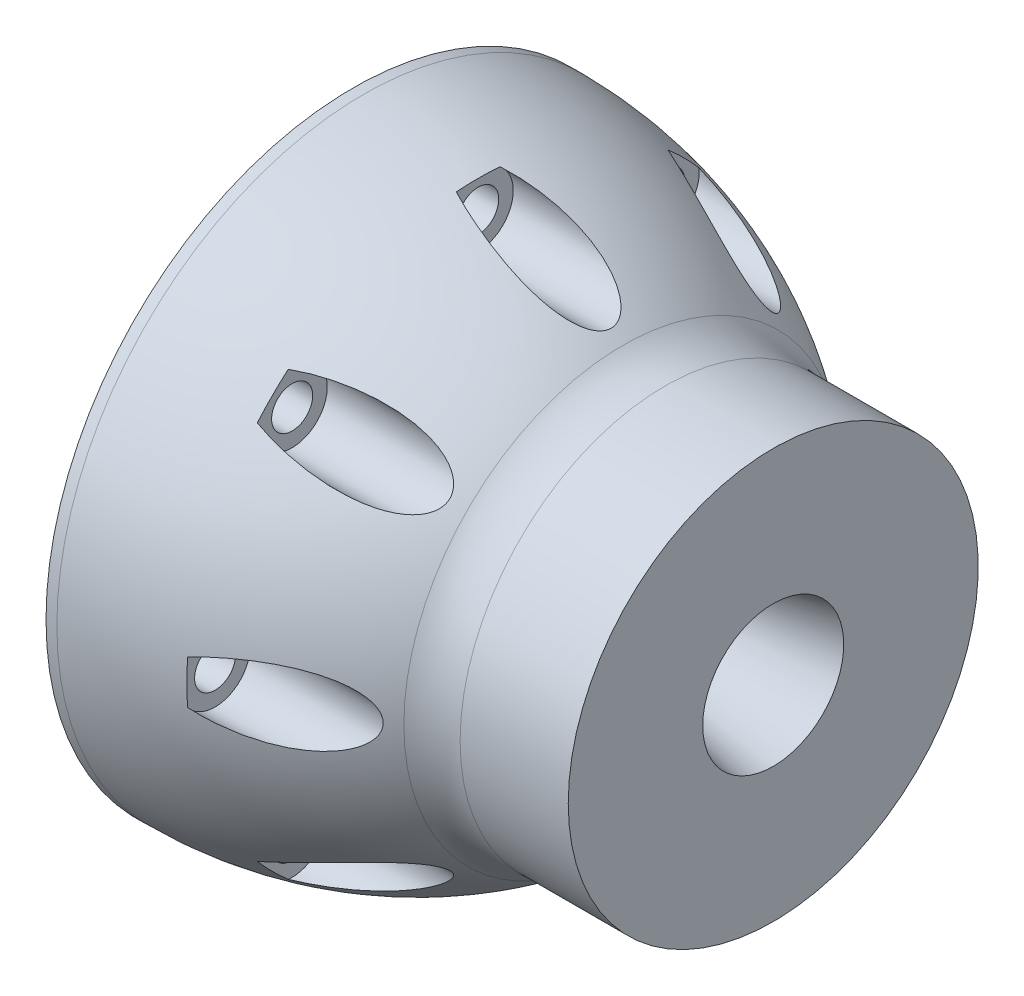
SolidWorks part; units mm, degrees
material "PLA (Polylactic Acid)"
ref_plane "Front Plane" through (0, 0, 0) normal (0, 0, 1) x (1, 0, 0)
ref_plane "Top Plane" through (0, 0, 0) normal (0, 1, 0) x (1, 0, 0)
ref_plane "Right Plane" through (0, 0, 0) normal (1, 0, 0) x (0, 0, -1)
sketch "Model" plane through (0, 0, 0) normal (0, 0, 1) x (1, 0, 0)
  line L0 (0, 19.051) -> (31.9536, 19.051)
  line L1 (38.3809, 16.3887) -> (49.0299, 5.7397)
  line L2 (0, 0) -> (61.8717, 0) construction
  arc A0 (38.3809, 16.3887) -> (31.9536, 19.051) centre (31.9536, 9.9615) ccw
  arc A1 (49.0299, 5.7397) -> (50.8, 5.0065) centre (50.8, 7.5097) ccw
  arc A2 (50.8, 5.0065) -> (51.2904, 5.055) centre (50.8, 7.5097) ccw
  spline S0 degree 2 poles (51.2904, 5.055) (61.5184, 7.0984) (61.8717, 7.148) knots 0 0 0 1 1 1
  text T0 "Vortex_Chamber_Cold_Wall" font "SWTXT" height 5
sketch "Sketch2" plane through (0, 0, 0) normal (0, 0, 1) x (1, 0, 0)
  line L0 (61.8717, 7.148) -> (51.2904, 5.055)
  line L1 (49.0299, 5.7397) -> (38.3809, 16.3887)
  line L2 (31.9536, 19.051) -> (25.6036, 19.051)
  line L3 (0, 19.051) -> (31.9536, 19.051) construction
  line L4 (25.6036, 19.051) -> (25.6036, 22.225)
  line L5 (0, 0) -> (61.8717, 0) construction
  line L6 (25.6036, 22.225) -> (19.2536, 22.225)
  line L7 (19.2536, 22.225) -> (19.2536, 31.115)
  line L8 (19.2536, 31.115) -> (20.3519, 31.115)
  line L9 (50.9079, 20.7844) -> (61.8717, 20.7844)
  line L10 (61.8717, 20.7844) -> (61.8717, 7.148)
  arc A0 (51.2904, 5.055) -> (50.8, 5.0065) centre (50.7951, 7.5588) cw
  arc A1 (50.8, 5.0065) -> (49.0299, 5.7397) centre (50.7953, 7.4983) cw
  arc A2 (38.3809, 16.3887) -> (31.9536, 19.051) centre (31.9536, 9.9614) ccw
  arc A3 (20.3519, 31.115) -> (46.6468, 22.225) centre (20.3519, -12.2178) cw
  arc A4 (46.6468, 22.225) -> (50.9079, 20.7844) centre (50.9079, 27.8064) ccw
  point P21 (19.2536, 26.67)
  dimension "D1" = 6.35
  dimension "D2" = 22.225
  dimension "D3" = 26.67
  dimension "D4" = 6.35
revolve "Revolve1" add sketch "Sketch2" angle 360 about L2
sketch "Sketch3" plane through (19.2536, 0, 0) normal (-1, 0, 0) x (0, 0, 1)
  line L0 (0, 22.225) -> (0, 31.115) construction
  circle A0 centre (0, 26.67) radius 3.556
  circle A1 centre (0, 0) radius 22.225 construction
  circle A2 centre (0, 0) radius 22.225 construction
  circle A3 centre (0, 0) radius 31.115 construction
  dimension "D1" = 7.112
extrude "Cut-Extrude1" cut sketch "Sketch3" against normal up to surface (42.6182 mm away) from offset 12.7 up to face at (61.8717, 0, 20.7844) offset against normal yes
sketch "Sketch4" plane through (31.9536, 0, 0) normal (1, 0, 0) x (0, 0, -1)
  circle A0 centre (0, 26.67) radius 2.0828
  dimension "D1" = 4.1656
extrude "Cut-Extrude2" cut sketch "Sketch4" against normal up to surface (12.7 mm away) up to face at (19.2536, 0, 22.225)
pattern_circular "CirPattern1" count 8 over 360 about axis through (0, 0, 0) along (1, 0, 0) of "Cut-Extrude2", "Cut-Extrude1"
sketch "Sketch5" plane through (0, 0, 0) normal (0, 0, 1) x (1, 0, 0)
  line L0 (25.6036, 19.051) -> (-53.7714, 19.051)
  dimension "D1" = 85.725
